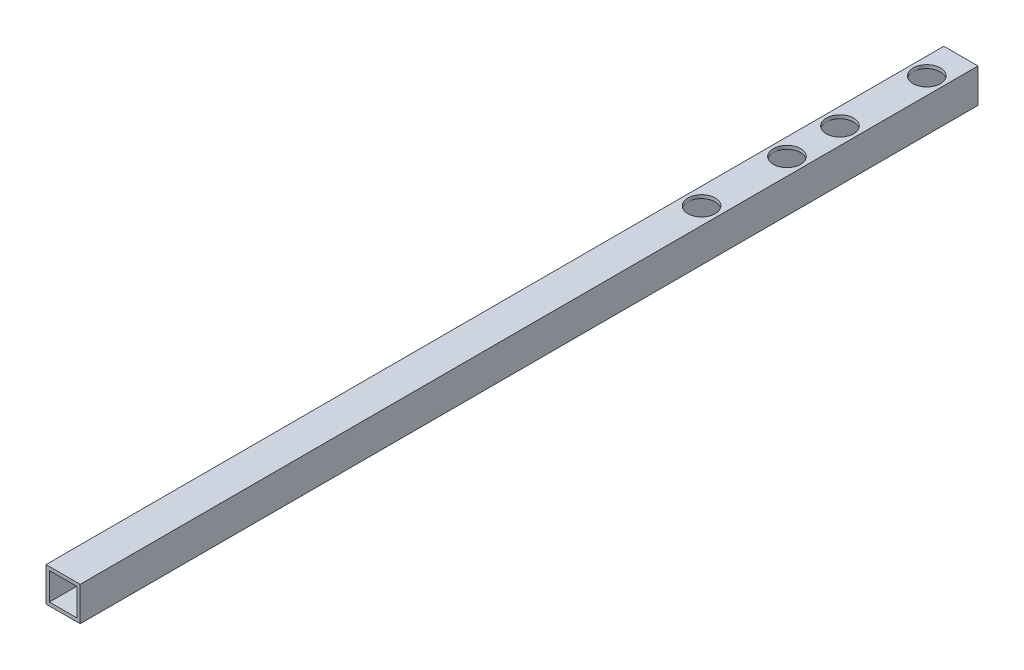
SolidWorks part; units mm, degrees
material "5052-H34"
ref_plane "正面" through (0, 0, 0) normal (0, 0, 1) x (1, 0, 0)
ref_plane "平面" through (0, 0, 0) normal (0, 1, 0) x (1, 0, 0)
ref_plane "右側面" through (0, 0, 0) normal (1, 0, 0) x (0, 0, -1)
sketch "ｽｹｯﾁ1" plane through (0, 0, 0) normal (0, 0, 1) x (1, 0, 0)
  line L1 (0, 0) -> (10, 0)
  line L2 (0, 0) -> (0, 10)
  line L3 (0, 10) -> (10, 10)
  line L4 (10, 0) -> (10, 10)
  dimension "D1" = 10
  dimension "D2" = 10
extrude "押し出し-薄板1" add sketch "ｽｹｯﾁ1" along normal blind 262.75 thin thin type one direction reverse wall 1
sketch "ｽｹｯﾁ2" plane through (0, 10, 0) normal (0, 1, 0) x (1, 0, 0)
  line L0 (5, 0) -> (5, -262.75) construction
  line L1 (10, 0) -> (0, 0) construction
  line L2 (10, -262.75) -> (0, -262.75) construction
  circle A0 centre (5, -75.9) radius 2
  circle A1 centre (5, -50.9) radius 2
  circle A2 centre (5, -35.4) radius 1.5
  circle A3 centre (5, -10) radius 1.5
  dimension "D1" = 4
  dimension "D2" = 50.9
  dimension "D3" = 25
  dimension "D4" = 35.4
  dimension "D5" = 10
  dimension "D6" = 3
extrude "ｶｯﾄ - 押し出し1" cut sketch "ｽｹｯﾁ2" against normal up to surface (10 mm away) up to face at (5, 0, 131.375)
sketch "ｽｹｯﾁ3" plane through (0, 10, 0) normal (0, 1, 0) x (1, 0, 0)
  circle A0 centre (5, -50.9) radius 4
  circle A1 centre (5, -75.9) radius 4
  circle A2 centre (5, -35.4) radius 4
  circle A3 centre (5, -10) radius 4
  dimension "D1" = 8
extrude "ｶｯﾄ - 押し出し2" cut sketch "ｽｹｯﾁ3" along direction (0, 1, 0) on the side against the normal up to surface (1 mm away) up to face at (5, 9, 73.9)
